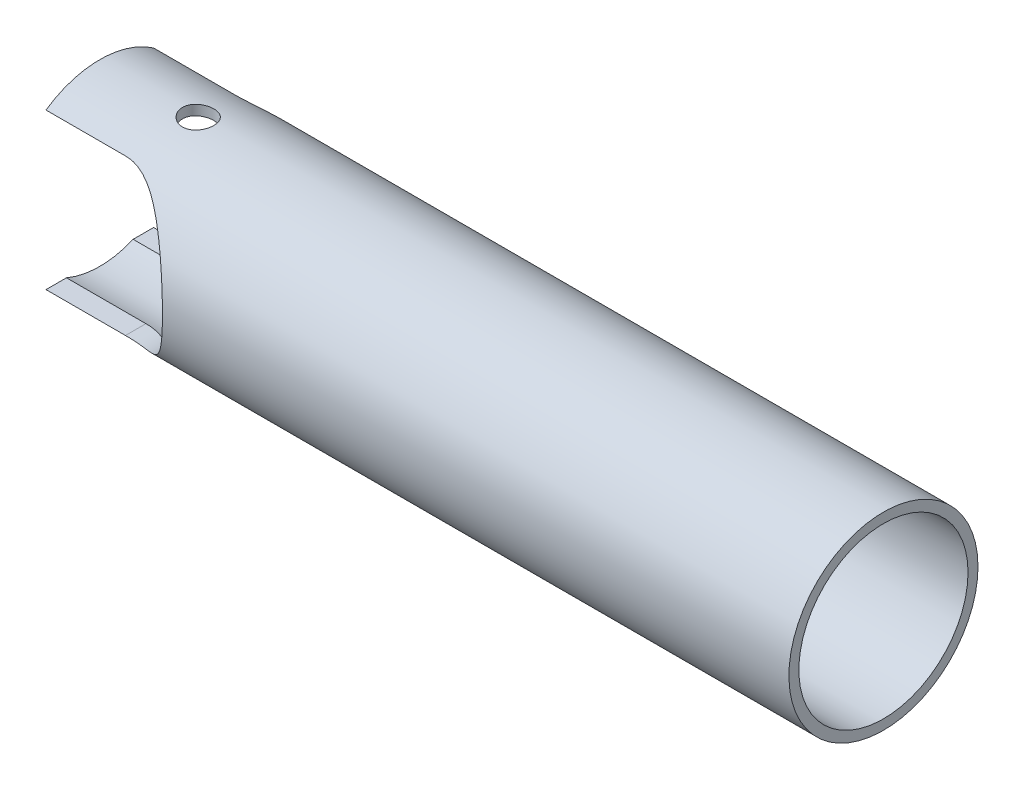
SolidWorks part; units mm, degrees
ref_plane "Front Plane" through (0, 0, 0) normal (0, 0, 1) x (1, 0, 0)
ref_plane "Top Plane" through (0, 0, 0) normal (0, 1, 0) x (1, 0, 0)
ref_plane "Right Plane" through (0, 0, 0) normal (1, 0, 0) x (0, 0, -1)
sketch "Sketch1" plane through (0, 0, 0) normal (1, 0, 0) x (0, 0, -1)
  circle A0 centre (0, 0) radius 1.0795
  circle A1 centre (0, 0) radius 1.2065
  dimension "D1" = 2.413
  dimension "D2" = 2.159
extrude "Boss-Extrude1" add sketch "Sketch1" along normal blind 10
sketch "Sketch2" plane through (0, 0, 0) normal (-1, 0, 0) x (0, 0, 1)
  line L0 (-1.2065, 0) -> (1.2065, 0) construction
  line L1 (-2.1976, -1.016) -> (2.4512, -1.016)
  line L2 (-2.1976, -1.016) -> (-2.1976, 1.016)
  line L3 (-2.1976, 1.016) -> (2.4512, 1.016)
  line L4 (2.4512, -1.016) -> (2.4512, 1.016)
  line L5 (-2.1976, 0) -> (2.4512, 0) construction
  circle A0 centre (0, 0) radius 1.2065 construction
  dimension "D1" = 2.032
sketch "Sketch5" plane through (0, 0, 0) normal (0, 0, 1) x (1, 0, 0)
  line L0 (0, 1.2065) -> (0, -1.2065) construction
  line L1 (0, 1.2065) -> (0, -1.2065) construction
  line L2 (1.0137, 0.9922) -> (1.0137, -0.9922) construction
  line L3 (1.0137, 0.9922) -> (0, 0.9922)
  line L4 (0, 0.9922) -> (0, -0.9922)
  line L6 (1.0137, -0.9922) -> (0, -0.9922)
  arc A0 (1.0137, 0.9922) -> (1.0137, -0.9922) centre (1.0137, 0) cw
  point P6 (0, 0)
  point P7 (0, 0)
  point P10 (1.5, -0.9922)
  dimension "D3" = 0.9922
  dimension "D4" = 1.9844
  dimension "D1" = 1.9844
  dimension "D2" = 1.5
extrude "Cut-Extrude4" cut sketch "Sketch5" against normal blind 10 and the other way blind 10
sketch "Sketch6" plane through (0, 0, 0) normal (0, 1, 0) x (1, 0, 0)
  line L0 (10, -1.0795) -> (10, 1.0795) construction
  line L1 (10, -1.0795) -> (10, 1.0795) construction
  line L2 (10, 0) -> (-1.9354, 0) construction
  line L3 (1.0137, -0.6864) -> (1.0137, -0.4253) construction
  circle A0 centre (1.2559, 0) radius 0.2
  dimension "D2" = 0.4
  dimension "D3" = 0.75
extrude "Cut-Extrude5" cut sketch "Sketch6" against normal blind 10 and the other way blind 10
equation "\"pin_hole_position\"= 0.75"
equation "\"pin_hole\"=0.4"
equation "\"D2@Sketch6\"=\"pin_hole\""
equation "\"D3@Sketch6\"=\"pin_hole_position\""
